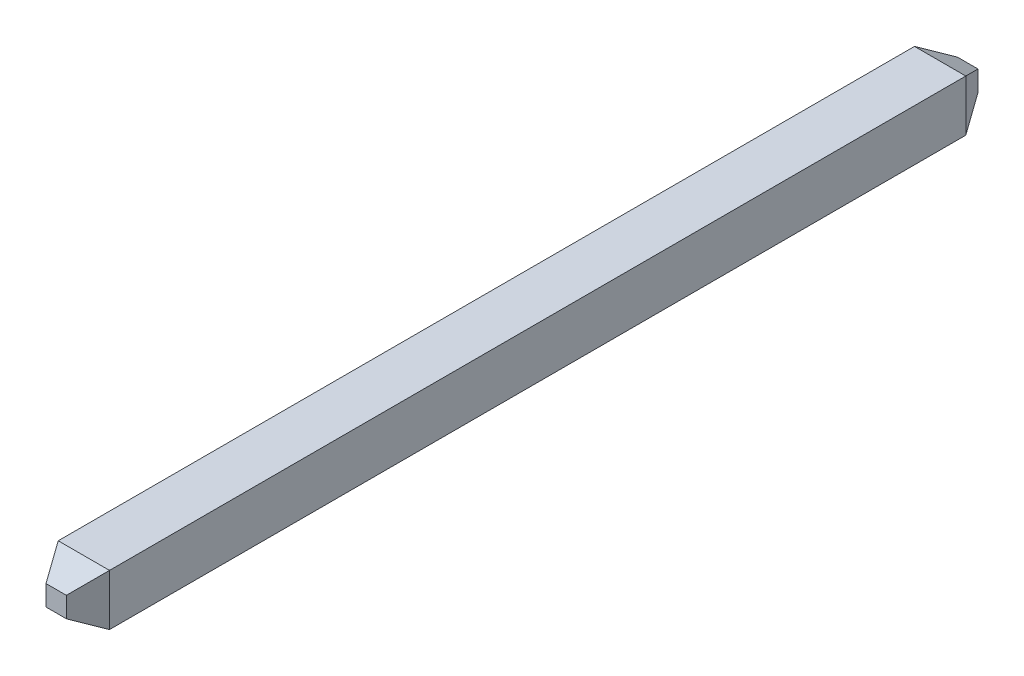
SolidWorks part; units mm, degrees
ref_plane "Front Plane" through (0, 0, 0) normal (0, 0, 1) x (1, 0, 0)
ref_plane "Top Plane" through (0, 0, 0) normal (0, 1, 0) x (1, 0, 0)
ref_plane "Right Plane" through (0, 0, 0) normal (1, 0, 0) x (0, 0, -1)
sketch "Sketch1" plane through (0, 0, 0) normal (0, 1, 0) x (1, 0, 0)
  line L5 (-0.3151, -5.6) -> (0.3151, -5.6)
  line L6 (-0.3151, -5.6) -> (-0.3151, 5.6)
  line L7 (-0.3151, 5.6) -> (0.3151, 5.6)
  line L8 (0.3151, -5.6) -> (0.3151, 5.6)
  line L9 (-0.3151, -5.6) -> (0.3151, 5.6) construction
  line L10 (-0.3151, 5.6) -> (0.3151, -5.6) construction
  point P0 (0.3151, -6.35)
  point P5 (0, 0)
  dimension "D1" = 11.2
  dimension "D2" = 0.6302
extrude "Boss-Extrude1" add sketch "Sketch1" against normal mid plane 0.63
chamfer "Chamfer1" distance 0.19 angle 60.803 8 edges at (-0.3151, 0, -5.6) (0, -0.315, -5.6) (0.3151, 0, -5.6) (0, 0.315, -5.6) (0.3151, 0, 5.6) (0, -0.315, 5.6) (-0.3151, 0, 5.6) (0, 0.315, 5.6) first distance on face at (0, 0, -5.6) first distance on face at (0, 0, 5.6)
